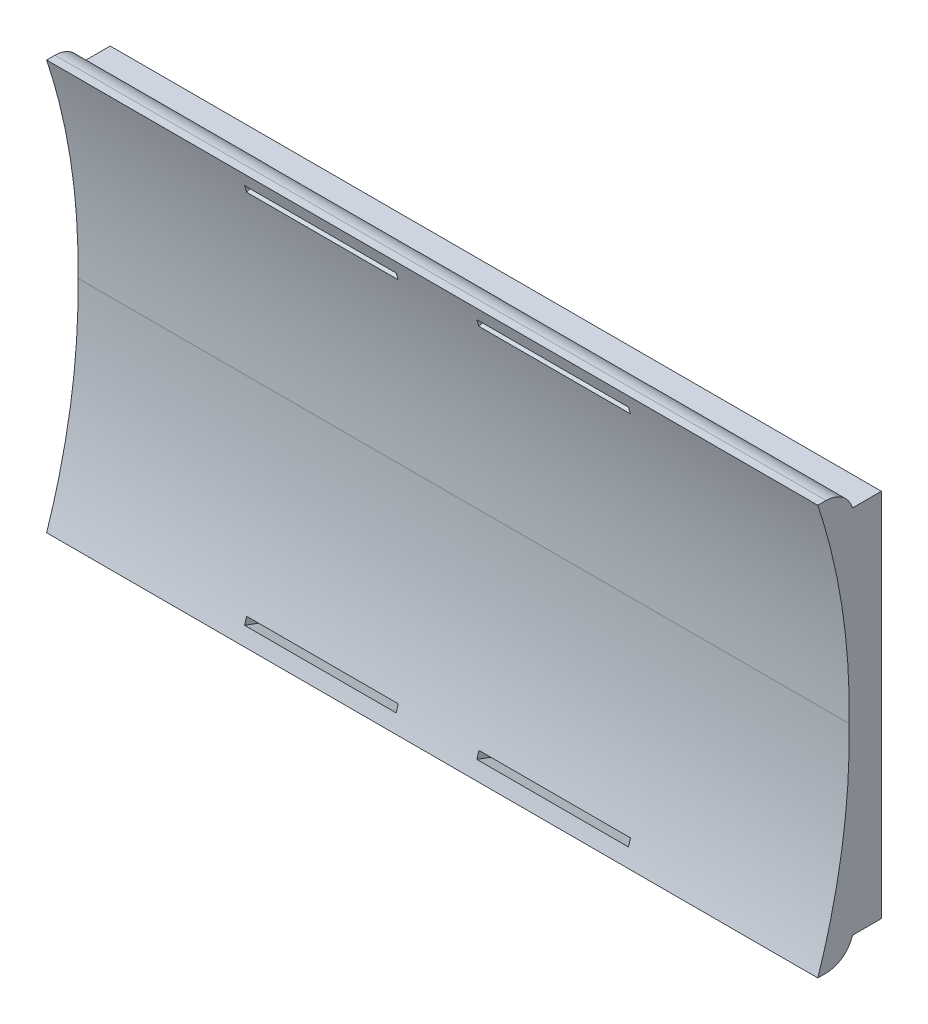
SolidWorks part; units mm, degrees
ref_plane "Front Plane" through (0, 0, 0) normal (0, 0, 1) x (1, 0, 0)
ref_plane "Top Plane" through (0, 0, 0) normal (0, 1, 0) x (1, 0, 0)
ref_plane "Right Plane" through (0, 0, 0) normal (1, 0, 0) x (0, 0, -1)
sketch "Sketch1" plane through (0, 0, 0) normal (0, 0, 1) x (1, 0, 0)
  line L0 (-54.75, 25.65) -> (-55.95, 25.65)
  line L1 (54.75, -25.65) -> (-54.75, -25.65)
  line L2 (54.75, -25.65) -> (54.75, 25.65)
  line L3 (54.75, 25.65) -> (-54.75, 25.65)
  line L4 (-54.75, -25.65) -> (-54.75, 25.65)
  line L5 (54.75, -25.65) -> (-54.75, 25.65) construction
  line L6 (54.75, 25.65) -> (-54.75, -25.65) construction
  line L7 (55.95, -26.85) -> (-55.95, -26.85)
  line L8 (55.95, -26.85) -> (55.95, 26.85)
  line L9 (55.95, 26.85) -> (-55.95, 26.85)
  line L10 (-55.95, -26.85) -> (-55.95, 26.85)
  line L11 (55.95, -26.85) -> (-55.95, 26.85) construction
  line L12 (55.95, 26.85) -> (-55.95, -26.85) construction
  line L13 (-54.75, -25.65) -> (-55.95, -25.65)
  point P0 (0, 0)
  point P6 (0, 0)
  dimension "D1" = 51.3
  dimension "D2" = 109.5
  dimension "D3" = 1.2
  dimension "D4" = 1.2
extrude "Boss-Extrude1" add sketch "Sketch1" along normal blind 3 contours L1 L13 L10 L7 L8 L9 L0 L3 L2 region at (-55.35, 25.7741, 0)
sketch "Sketch2" plane through (0, 0, 3) normal (0, 0, 1) x (1, 0, 0)
  line L1 (55.95, -26.85) -> (-55.95, -26.85)
  line L2 (55.95, -26.85) -> (55.95, 26.85)
  line L3 (55.95, 26.85) -> (-55.95, 26.85)
  line L4 (-55.95, -26.85) -> (-55.95, 26.85)
  line L5 (55.95, -26.85) -> (-55.95, 26.85) construction
  line L6 (55.95, 26.85) -> (-55.95, -26.85) construction
  point P0 (0, 0)
extrude "Boss-Extrude2" add sketch "Sketch2" along normal blind 1.2
sketch "Sketch3" plane through (55.95, 0, 0) normal (1, 0, 0) x (0, 0, -1)
  line L0 (-4.2, -26.8862) -> (-5.2252, -29.7027)
  line L1 (0, 0) -> (27.0007, 0) construction
  line L2 (-4.2, -26.8862) -> (-4.2, 26.8862)
  line L3 (-4.2, -26.85) -> (-4.2, 26.85) construction
  line L4 (-5.2252, -29.7027) -> (-9.2252, -29.7027)
  line L5 (-5.2252, 29.7027) -> (-9.2252, 29.7027)
  line L6 (-4.2, 26.8862) -> (-5.2252, 29.7027)
  line L7 (-4.2, -26.85) -> (0, -26.85) construction
  line L8 (-4.2, 26.85) -> (-4.2, -26.85) construction
  spline S0 degree 2 poles (-4.6714, 0) (-4.4393, -15.2584) (-9.2252, -29.7027) knots 0 0 0 1 1 1
  spline S1 degree 2 poles (-4.6714, 0) (-4.4393, 15.2584) (-9.2252, 29.7027) knots 0 0 0 1 1 1
  point P18 (-4.2, 0)
  line M3 (-4.2, 26.85) -> (-4.2, -26.85)
  dimension "D3" = 110
  dimension "D1" = 4
extrude "Boss-Extrude3" add sketch "Sketch3" against normal up to vertex (111.9 mm away) contours S0 L4 L0 M3 | S1 L6 L5 M3 region at (55.95, -28.0905, 5.2728) up to point (-55.95, -26.85, 4.2)
sketch "Sketch4" plane through (0, 1.7952, -4.9324) normal (0, 0.342, -0.9397) x (-1, 0, 0)
  line L0 (55.95, 29.6986) -> (-55.95, 29.6986) construction
  line L1 (27.8846, 27.8627) -> (-27.8154, 27.8627)
  line L2 (27.8846, 27.8627) -> (27.8846, 28.8986)
  line L3 (27.8846, 28.8986) -> (-27.8154, 28.8986)
  line L4 (-27.8154, 27.8627) -> (-27.8154, 28.8986)
  line L5 (27.8846, 27.8627) -> (-27.8154, 28.8986) construction
  line L6 (27.8846, 28.8986) -> (-27.8154, 27.8627) construction
  line L7 (-55.95, 26.6627) -> (55.95, 26.6627) construction
  line L11 (-5.8154, 27.8627) -> (5.8846, 27.8627)
  line L12 (-5.8154, 27.8627) -> (-5.8154, 28.8986)
  line L13 (-5.8154, 28.8986) -> (5.8846, 28.8986)
  line L14 (5.8846, 27.8627) -> (5.8846, 28.8986)
  line L15 (-5.8154, 27.8627) -> (5.8846, 28.8986) construction
  line L16 (-5.8154, 28.8986) -> (5.8846, 27.8627) construction
  line L17 (0, 29.6986) -> (0, 26.7012) construction
  line L18 (55.95, 26.7012) -> (-55.95, 26.7012) construction
  point P0 (0.0346, 28.3806)
  point P13 (0.0346, 28.3806)
  dimension "D1" = 0.8
  dimension "D2" = 1.2
  dimension "D4" = 11.7
  dimension "D5" = 22
extrude "Cut-Extrude1" cut sketch "Sketch4" against normal blind 20 contours L1 L12 L3 L4 | L14 L1 L2 L3 region at (-16.8846, 28.4643, 4.7744) region at (16.8154, 28.4643, 4.7744)
mirror "Mirror1" about plane through (0, 0, 0) normal (0, 1, 0) of "Cut-Extrude1"
fillet "Fillet1" radius 4 2 edges at (0, 29.7027, 5.2252) (0, -29.7027, 5.2252)
sketch "Sketch5" plane through (0, 0, 0) normal (0, 0, -1) x (-1, 0, 0)
  line L0 (55.95, -26.8862) -> (-55.95, -26.8862) construction
  line L1 (55.95, -25.65) -> (30.95, -25.65)
  line L2 (55.95, -25.65) -> (55.95, -26.8862)
  line L3 (55.95, -26.8862) -> (30.95, -26.8862)
  line L4 (30.95, -25.65) -> (30.95, -26.8862)
  dimension "D1" = 25
extrude "Cut-Extrude2" cut sketch "Sketch5" against normal up to surface (3 mm away) up to face at (-0.6, 0, 3)
